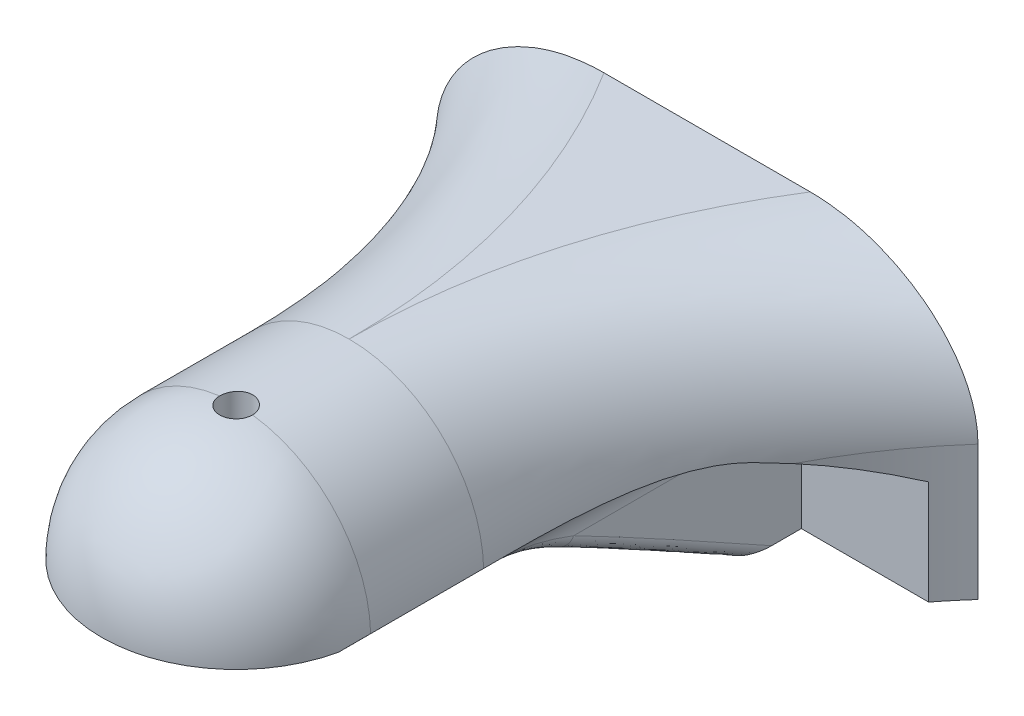
SolidWorks part; units mm, degrees
material "ABS"
ref_plane "Plan de face" through (0, 0, 0) normal (0, 0, 1) x (1, 0, 0)
ref_plane "Plan de dessus" through (0, 0, 0) normal (0, 1, 0) x (1, 0, 0)
ref_plane "Plan de droite" through (0, 0, 0) normal (1, 0, 0) x (0, 0, -1)
sketch "Esquisse1" plane through (0, 0, 0) normal (0, 1, 0) x (1, 0, 0)
  line L0 (0, 0) -> (0, -60) construction
  line L1 (0, -60) -> (-20.1285, -60)
  line L2 (0, -60) -> (0, -105)
  line L3 (-10, -95) -> (-10, -86.6025)
  line L4 (0, 0) -> (-50, -86.6025) construction
  arc A0 (0, -105) -> (-10, -95) centre (0, -95) cw
  arc A1 (-10, -86.6025) -> (-20.1285, -60) centre (-50, -86.6025) ccw
  dimension "D1" = 60
  dimension "D3" = 10
  dimension "D5" = 40
  dimension "D2" = 95
  dimension "D4" = 100
  dimension "D6" = 30
extrude "Boss.-Extru.1" add sketch "Esquisse1" along normal blind 20 from offset 8 offset against normal yes
fillet "Congé1" radius 10 3 edges at (-7.0711, 12, 102.0711) (-10, 12, 90.8013) (-12.6178, 12, 72.3698)
sketch "Esquisse2" plane through (0, 0, 0) normal (0, 1, 0) x (1, 0, 0)
  line L0 (-12, -60) -> (-12, -15) construction
  line L1 (0, -60) -> (-20.1285, -60) construction
  line L2 (-12, -60) -> (-12, -105)
  line L3 (-12, -105) -> (-9, -105)
  line L4 (-9, -105) -> (-9, -62)
  line L5 (-9, -62) -> (-10.5, -62)
  line L6 (-10.5, -62) -> (-10.5, -60)
  line L7 (-10.5, -60) -> (-12, -60)
  line L8 (0, -105) -> (0, -60) construction
  dimension "D1" = 2
  dimension "D2" = 12
  dimension "D3" = 3
  dimension "D4" = 6
revolve "Enlèvement de matière-Révolution1" cut sketch "Esquisse2" angle 360 about L0
sketch "Esquisse3" plane through (0, 0, 62) normal (0, 0, 1) x (1, 0, 0)
  line L1 (-20.1285, -8) -> (-9, -8)
  line L2 (-20.1285, -8) -> (-20.1285, -1.2289)
  line L3 (-20.1285, -1.2289) -> (-13.5, 2.5981)
  line L4 (-9, -8) -> (-9, 0)
  circle A0 centre (-12, 0) radius 3 construction
  arc A1 (-9, 0) -> (-13.5, 2.5981) centre (-12, 0) ccw
  dimension "D1" = 60
extrude "Enlèv. mat.-Extru.1" cut sketch "Esquisse3" along normal through all
sketch "Esquisse4" plane through (0, -8, 0) normal (0, -1, 0) x (1, 0, 0)
  line L0 (0, 105) -> (0, 60) construction
  circle A0 centre (0, 95) radius 1.225
  arc A1 (0, 105) -> (-9, 99.3589) centre (0, 95) ccw construction
  dimension "D1" = 2.45
extrude "Enlèv. mat.-Extru.2" cut sketch "Esquisse4" against normal through all
sketch "Esquisse5" plane through (0, -8, 0) normal (0, -1, 0) x (1, 0, 0)
  circle A0 centre (0, 95) radius 12.5
  dimension "D1" = 25
extrude "Enlèv. mat.-Extru.3" cut sketch "Esquisse5" along normal blind 10 draft 60 from offset 10 draft outward yes offset against normal yes
fillet "Congé2" radius 1 2 edges
sketch "Esquisse6" plane through (0, 2, 0) normal (0, -1, 0) x (1, 0, 0)
  line L2 (0, 96.225) -> (0, 101)
  line L3 (0, 89) -> (0, 93.775)
  line L4 (0, 82.5) -> (0, 93.775) construction
  line L5 (0, 96.225) -> (0, 105) construction
  arc A0 (0, 101) -> (0, 89) centre (0, 95) ccw
  arc A2 (0, 96.225) -> (0, 93.775) centre (0, 95) ccw
  arc A3 (0, 96.225) -> (0, 93.775) centre (0, 95) ccw construction
  dimension "D1" = 6
extrude "Boss.-Extru.2" add sketch "Esquisse6" along normal blind 0.5
mirror "Symétrie1" about plane through (0, 12, 60) normal (-1, 0, 0) of bodies 106
chamfer "Chanfrein1" distance 0.5 angle 45 1 edges at (0, 2, 89)
